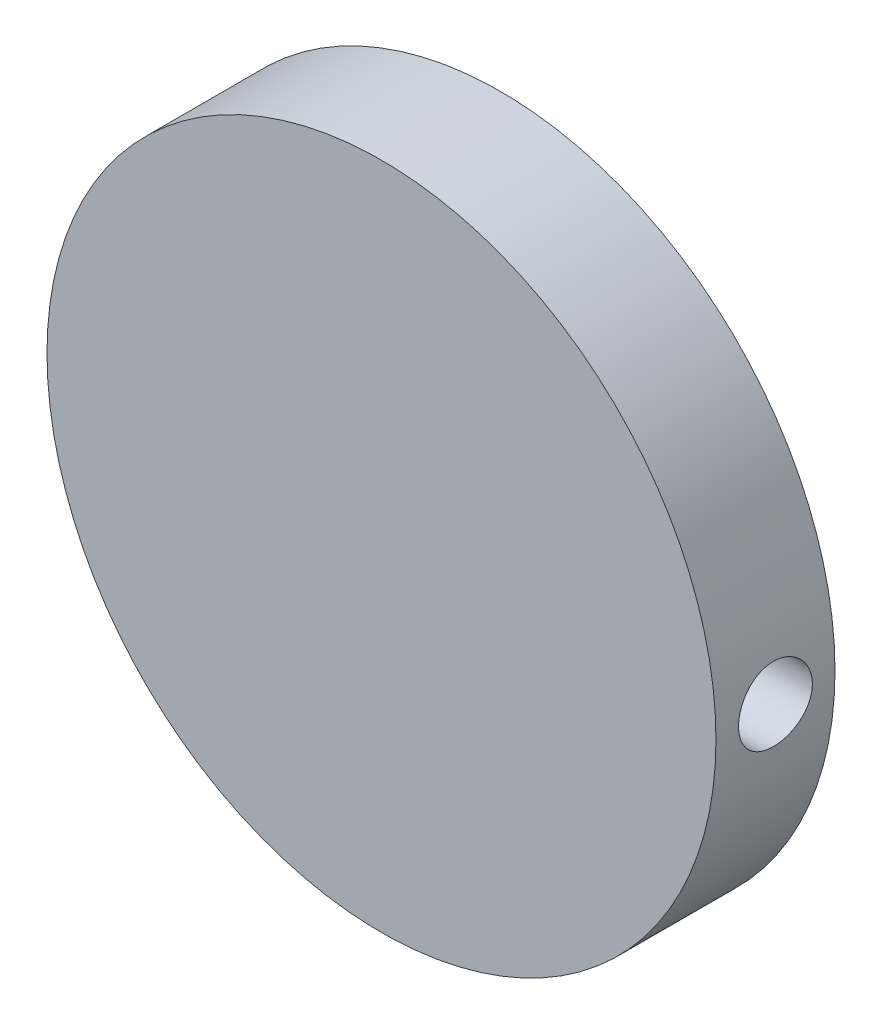
SolidWorks part; units mm, degrees
ref_plane "Front" through (0, 0, 0) normal (0, 0, 1) x (1, 0, 0)
ref_plane "Top" through (0, 0, 0) normal (0, 1, 0) x (1, 0, 0)
ref_plane "Right" through (0, 0, 0) normal (1, 0, 0) x (0, 0, -1)
sketch "Sketch1" plane through (0, 0, 0) normal (0, 0, 1) x (1, 0, 0)
  circle A0 centre (0, 0) radius 14.05
extrude "Extrude1" add sketch "Sketch1" along normal blind 5
sketch "Sketch2" plane through (0, 0, 0) normal (1, 0, 0) x (0, 0, -1)
  line L0 (-5, 0) -> (0, 0) construction
  circle A0 centre (-2.5, 0) radius 1.55
extrude "Cut-Extrude1" cut sketch "Sketch2" against normal through all and the other way through all
sketch "Sketch3" plane through (0, 0, 0) normal (0, 0, -1) x (-1, 0, 0)
  circle A0 centre (0, 0) radius 11.1125
extrude "Cut-Extrude2" cut sketch "Sketch3" against normal blind 2.5
